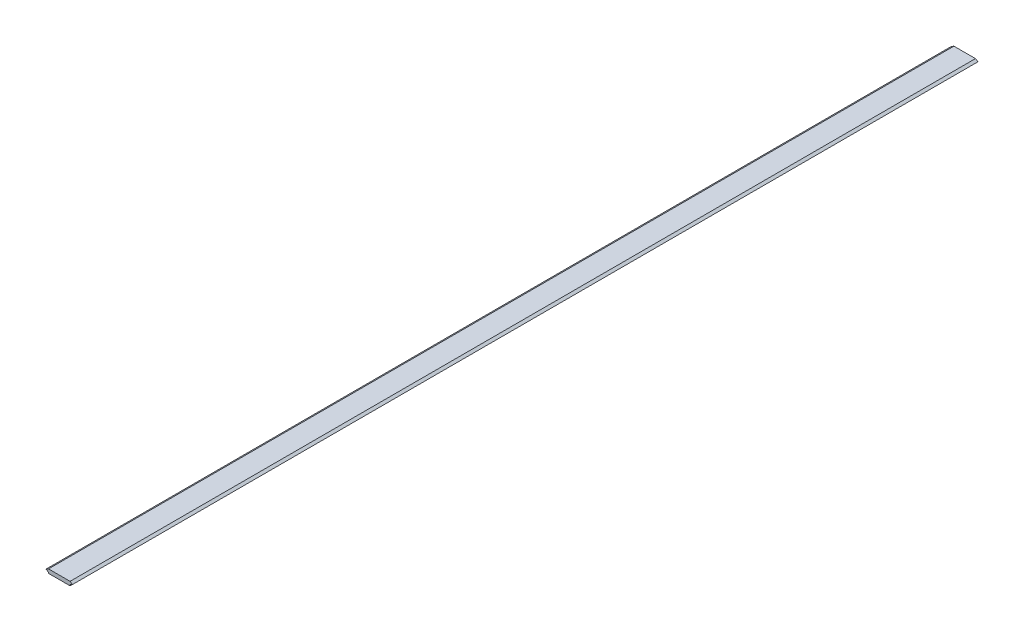
SolidWorks part; units mm, degrees
ref_plane "Front Plane" through (0, 0, 0) normal (0, 0, 1) x (1, 0, 0)
ref_plane "Top Plane" through (0, 0, 0) normal (0, 1, 0) x (1, 0, 0)
ref_plane "Right Plane" through (0, 0, 0) normal (1, 0, 0) x (0, 0, -1)
sketch "Sketch1" plane through (0, 0, 0) normal (0, 0, 1) x (1, 0, 0)
  line L0 (0, 0) -> (22, 0)
  line L1 (22, 0) -> (24.5981, -1.5)
  line L2 (24.5981, -1.5) -> (22, -3)
  line L3 (22, -3) -> (22, -4)
  line L4 (22, -4) -> (0, -4)
  line L5 (0, -4) -> (0, -3)
  line L6 (0, -3) -> (-2.5981, -1.5)
  line L7 (-2.5981, -1.5) -> (0, 0)
  dimension "D1" = 22
  dimension "D2" = 3
  dimension "D3" = 60
  dimension "D4" = 1
  dimension "D5" = 2.5
extrude "Boss-Extrude1" add sketch "Sketch1" along normal blind 925
equation "\"SlotWidth\"= 22mm"
equation "\"WedgeAngle\"= 60deg"
equation "\"WedgeHeight\"= 3mm"
equation "\"WedgeMidDistance\"= 2.5mm"
equation "\"WedgeDistance\"= 1mm"
equation "\"D1@Sketch1\"= \"SlotWidth\""
equation "\"D2@Sketch1\"= \"WedgeHeight\""
equation "\"D3@Sketch1\"= \"WedgeAngle\""
equation "\"D4@Sketch1\"= \"WedgeDistance\""
equation "\"D5@Sketch1\"= \"WedgeMidDistance\""
equation "\"AxialLength\"= 925mm"
equation "\"D1@Boss-Extrude1\"= \"AxialLength\""
